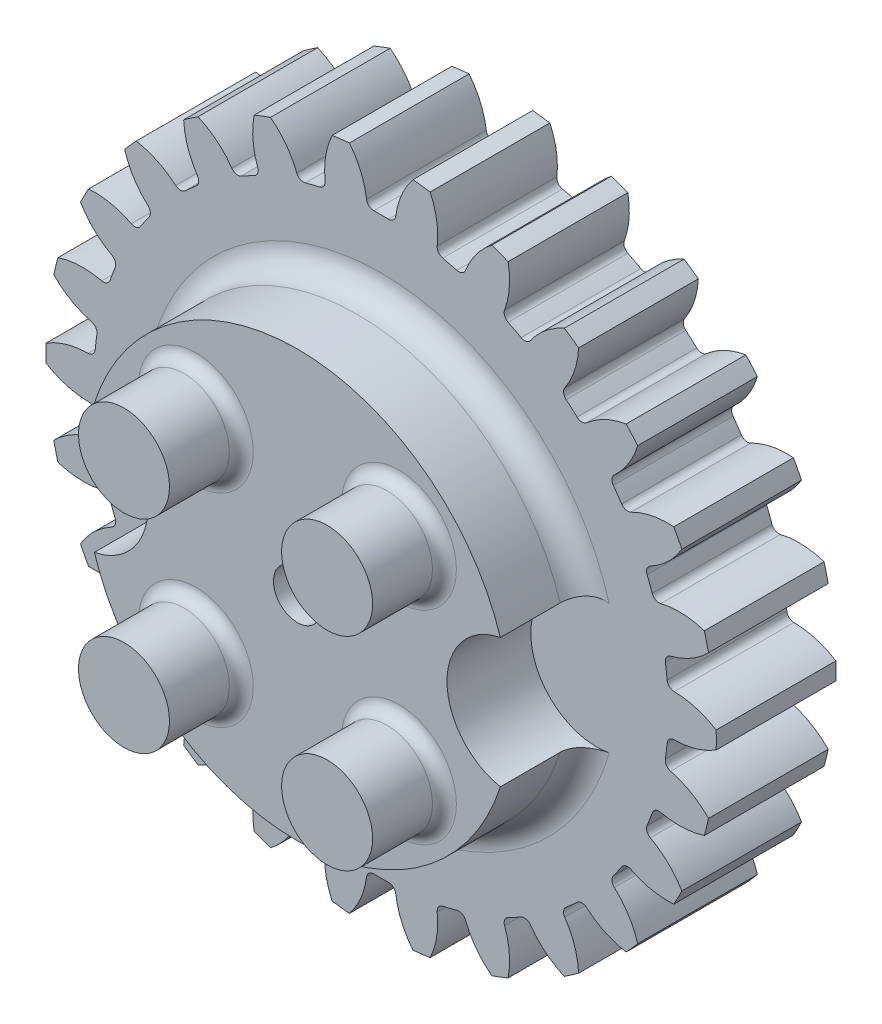
SolidWorks part; units mm, degrees
ref_plane "Front" through (0, 0, 0) normal (0, 0, 1) x (1, 0, 0)
ref_plane "Top" through (0, 0, 0) normal (0, 1, 0) x (1, 0, 0)
ref_plane "Right" through (0, 0, 0) normal (1, 0, 0) x (0, 0, -1)
sketch "Sketch1" plane through (0, 0, 0) normal (0, 0, 1) x (1, 0, 0)
  circle A0 centre (0, 0) radius 12
  circle A1 centre (0, 0) radius 14
  circle A2 centre (0, 0) radius 13
  dimension "D1" = 28
  dimension "D2" = 24
  dimension "D3" = 26
extrude "Boss-Extrude1" add sketch "Sketch1" along normal mid plane 5 contours A1
sketch "Sketch3" plane through (0, 0, 0) normal (0, 0, 1) x (1, 0, 0)
  line L0 (0, 0) -> (0, 14) construction
  line L1 (0, 0) -> (-0.5852, 11.9857) construction
  line L2 (-0.7849, 12.9763) -> (0.7849, 12.9763) construction
  line L3 (0, 10.8197) -> (-1.1406, 13.9535) construction
  line L4 (0, 0) -> (1.6875, 13.8979) construction
  line L5 (0.7849, 12.9763) -> (2.3433, 12.7871) construction
  circle A7 centre (0, 0) radius 14 construction
  arc A10 (-1.3262, 13.937) -> (-0.5852, 11.9857) centre (-3.9591, 11.821) cw
  arc A11 (1.3262, 13.937) -> (0.5852, 11.9857) centre (3.9591, 11.821) ccw
  circle A12 centre (0, 0) radius 12 construction
  arc A13 (-0.5852, 11.9857) -> (0.5852, 11.9857) centre (0, 0) cw
  arc A14 (-1.3262, 13.937) -> (1.3262, 13.937) centre (0, 0) cw
  circle A15 centre (0, 0) radius 13 construction
  dimension "D1" = 20
  dimension "D2" = 6.923
extrude "Cut-Extrude1" cut sketch "Sketch3" against normal through all both and the other way through all
fillet "Fillet2" radius 0.3 2 edges at (0.5852, 11.9857, 0) (-0.5852, 11.9857, 0)
pattern_circular "CirPattern1" count 26 over 360 about axis through (0, 0, 2.5) along (0, 0, -1) of "Cut-Extrude1", "Fillet2"
sketch "Sketch6" plane through (0, 0, 2.5) normal (0, 0, 1) x (1, 0, 0)
  line L0 (0, -9) -> (0, 9) construction
  line L1 (9, 0) -> (-9, 0) construction
  line L2 (-4.2426, -4.2426) -> (4.2426, 4.2426) construction
  line L3 (-4.2426, 4.2426) -> (4.2426, -4.2426) construction
  circle A0 centre (4.2426, 4.2426) radius 1.9 construction
  circle A1 centre (4.2426, -4.2426) radius 1.9 construction
  circle A2 centre (-4.2426, -4.2426) radius 1.9 construction
  circle A3 centre (-4.2426, 4.2426) radius 1.9 construction
  arc A4 (-8.4804, -2.7005) -> (-8.4804, 2.7005) centre (-9, 0) ccw
  arc A5 (8.4804, -2.7005) -> (8.4804, 2.7005) centre (9, 0) cw
  arc A6 (-8.4804, 2.7005) -> (8.4804, 2.7005) centre (0, 0) cw
  arc A7 (-8.4804, -2.7005) -> (8.4804, -2.7005) centre (0, 0) ccw
  dimension "D4" = 3.8
  dimension "D5" = 2.75
  dimension "D6" = 8.9
  dimension "D1" = 18
  dimension "D2" = 12
  dimension "D3" = 45
extrude "Boss-Extrude2" add sketch "Sketch6" along normal blind 3.5
sketch "Sketch7" plane through (0, 0, 6) normal (0, 0, 1) x (1, 0, 0)
  circle A0 centre (-4.2426, 4.2426) radius 1.9
  circle A1 centre (4.2426, 4.2426) radius 1.9
  circle A2 centre (4.2426, -4.2426) radius 1.9
  circle A3 centre (-4.2426, -4.2426) radius 1.9
  dimension "D1" = 3.8
extrude "Boss-Extrude3" add sketch "Sketch7" along normal blind 3
fillet "Fillet3" radius 1 2 edges at (0, -8.9, 2.5) (0, 8.9, 2.5)
fillet "Fillet4" radius 0.5 4 edges at (-2.3426, -4.2426, 6) (6.1426, -4.2426, 6) (6.1426, 4.2426, 6) (-2.3426, 4.2426, 6)
sketch "Sketch8" plane through (0, 0, -2.5) normal (0, 0, -1) x (-1, 0, 0)
  circle A0 centre (0, 0) radius 1
  dimension "D1" = 2
extrude "Through_Center_Hole" cut sketch "Sketch8" against normal through all
equation "\"od\"= 28'outside diameter"
equation "\"n\"= 26'number of teeth"
equation "\"m\"= \"od\" / ( \"n\" + 2 )'module"
equation "\"p\"= \"m\" * pi'pitch"
equation "\"d\"= \"m\" * \"n\"'primitive diameter"
equation "\"da\"= \"d\" + 2 * \"m\"'head diamater"
equation "\"df\"= \"d\" - 2 * \"m\"'foot diameter"
equation "\"D1@Sketch1\"=\"od\""
equation "\"D2@Sketch1\"=\"df\""
equation "\"D3@Sketch1\"=\"d\""
equation "\"D2@Sketch3\"=180/\"n\""
equation "\"D1@Fillet2\"=.3*\"m\""
equation "\"D1@CirPattern1\"=\"n\""
